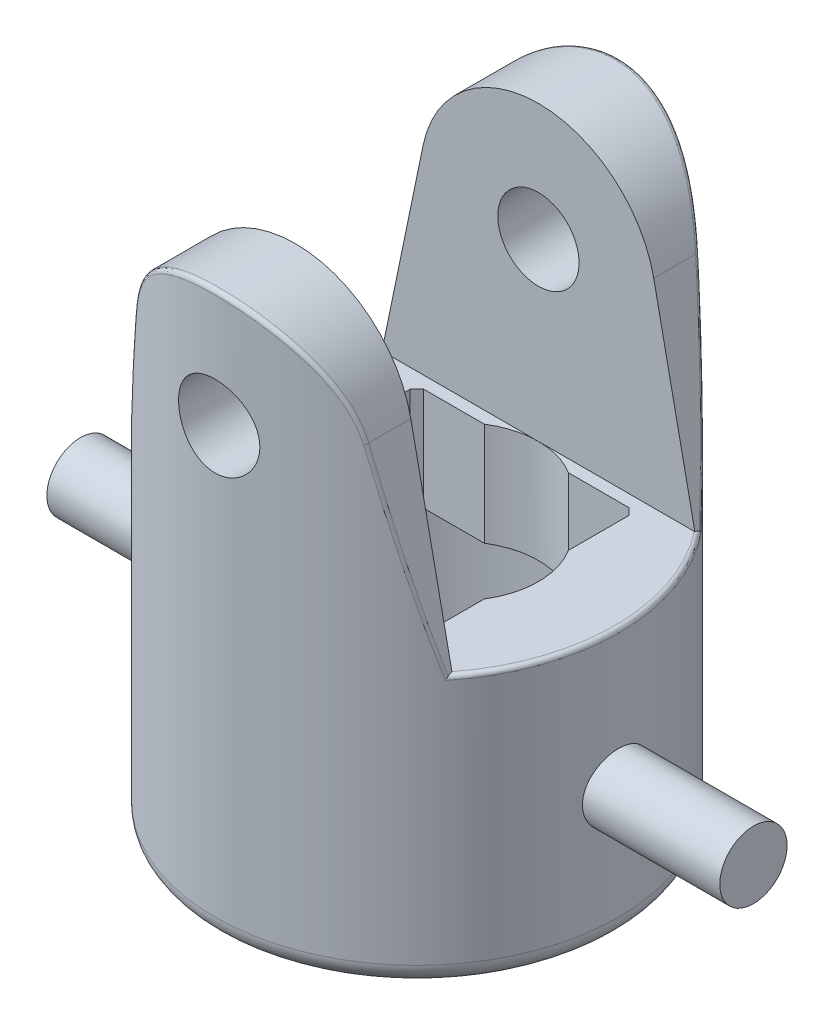
SolidWorks part; units mm, degrees
material "1023 Carbon Steel Sheet (SS)"
ref_plane "Front Plane" through (0, 0, 0) normal (0, 0, 1) x (1, 0, 0)
ref_plane "Top Plane" through (0, 0, 0) normal (0, 1, 0) x (1, 0, 0)
ref_plane "Right Plane" through (0, 0, 0) normal (1, 0, 0) x (0, 0, -1)
sketch "Sketch1" plane through (0, 0, 0) normal (0, 1, 0) x (1, 0, 0)
  circle A0 centre (0, 0) radius 12
  dimension "D1" = 24
extrude "Boss-Extrude1" add sketch "Sketch1" along normal blind 33.53
sketch "Sketch2" plane through (0, 0, 0) normal (0, -1, 0) x (1, 0, 0)
  line L0 (-2.5, 6.5) -> (-6.1, 6.5)
  line L1 (6.5, -6.5) -> (-6.5, -6.5) construction
  line L2 (6.5, -6.5) -> (6.5, 6.5) construction
  line L3 (-6.5, 6.1) -> (-6.5, 2.5)
  line L4 (-6.5, -6.5) -> (-6.5, 6.5) construction
  line L5 (6.5, -6.5) -> (-6.5, 6.5) construction
  line L6 (6.5, 6.5) -> (-6.5, -6.5) construction
  line L7 (-6.5, -2.5) -> (-6.5, -6.1)
  line L8 (-6.1, -6.5) -> (-2.5, -6.5)
  line L9 (2.5, -6.5) -> (6.1, -6.5)
  line L10 (6.5, -6.1) -> (6.5, -2.5)
  line L11 (6.5, 2.5) -> (6.5, 6.1)
  line L12 (6.1, 6.5) -> (2.5, 6.5)
  line L13 (-6.1, 6.5) -> (-6.5, 6.1)
  line L14 (-6.5, -6.1) -> (-6.1, -6.5)
  line L15 (6.1, -6.5) -> (6.5, -6.1)
  line L16 (6.5, 6.1) -> (6.1, 6.5)
  arc A0 (-2.5, 6.5) -> (2.5, 6.5) centre (0, 2.5201) cw
  arc A1 (6.5, 2.5) -> (6.5, -2.5) centre (2.5201, 0) cw
  arc A2 (2.5, -6.5) -> (-2.5, -6.5) centre (0, -2.5201) cw
  arc A3 (-6.5, -2.5) -> (-6.5, 2.5) centre (-2.5201, 0) cw
  point P0 (0, 0)
  point P21 (0, 0)
  dimension "D3" = 4.7
  dimension "D4" = 4
  dimension "D1" = 13
  dimension "D2" = 4
extrude "Cut-Extrude1" cut sketch "Sketch2" against normal blind 19.6
sketch "Sketch3" plane through (0, 0, 0) normal (0, -1, 0) x (1, 0, 0)
  circle A0 centre (0, 0) radius 9.375
  dimension "D1" = 18.75
fillet "Fillet1" radius 1.25 1 edges at (0, 0, 12)
sketch "Sketch4" plane through (0, 0, 0) normal (0, 0, 1) x (1, 0, 0)
  line L0 (-7.2, 5.7) -> (-7.2, 4.7)
  line L1 (-7.2, 4.7) -> (-6.6396, 4.9757)
  line L2 (-6.6396, 5.4243) -> (-7.2, 5.7)
  line L3 (-6.5, 19.6) -> (-6.5, 0) construction
  arc A0 (-6.6396, 4.9757) -> (-6.6396, 5.4243) centre (-6.75, 5.2) ccw
  point P5 (-6.1837, 5.2)
  dimension "D3" = 0.25
  dimension "D1" = 1
  dimension "D2" = 7.2
  dimension "D4" = 4.7
extrude "Boss-Extrude2" add sketch "Sketch4" against normal up to surface and the other way up to surface up to face at (-6.86, 9.8, 0) other way up to face at (-6.86, 9.8, 0)
ref_axis "Axis1" through (0, 35.4242, 0) along (0, -1, 0)
pattern_circular "CirPattern2" count 4 over 360 about axis through (0, 35.4242, 0) along (0, -1, 0) of "Boss-Extrude2"
sketch "Sketch5" plane through (0, 33.53, 0) normal (0, 1, 0) x (1, 0, 0)
  line L1 (12, -7.2201) -> (-12, -7.2201)
  line L2 (12, -7.2201) -> (12, 7.2201)
  line L3 (12, 7.2201) -> (-12, 7.2201)
  line L4 (-12, -7.2201) -> (-12, 7.2201)
  line L5 (12, -7.2201) -> (-12, 7.2201) construction
  line L6 (12, 7.2201) -> (-12, -7.2201) construction
  arc A0 (2.5, 6.5) -> (-2.5, 6.5) centre (0, 2.5201) ccw construction
  circle A1 centre (0, 0) radius 12 construction
  point P0 (0, 0)
extrude "Cut-Extrude3" cut sketch "Sketch5" against normal blind 17.4
sketch "Sketch6" plane through (0, 0, 0) normal (0, 0, 1) x (1, 0, 0)
  line L0 (12, 16.13) -> (9.3, 16.13)
  line L1 (9.3, 16.13) -> (6.8548, 27.9483)
  line L2 (-6.8548, 27.9483) -> (-9.3, 16.13)
  line L3 (-9.3, 16.13) -> (-12, 16.13)
  line L4 (9.5849, 33.53) -> (-9.5849, 33.53) construction
  arc A0 (6.8548, 27.9483) -> (-6.8548, 27.9483) centre (0, 26.53) ccw
  dimension "D2" = 7
  dimension "D1" = 2.7
extrude "Cut-Extrude6" cut sketch "Sketch6" against normal through all both and the other way through all flip side to cut
sketch "Sketch7" plane through (0, 0, 0) normal (0, 0, 1) x (1, 0, 0)
  circle A0 centre (0, 26.53) radius 2.415
  dimension "D1" = 4.83
extrude "Cut-Extrude7" cut sketch "Sketch7" against normal mid plane 52.4
fillet "Fillet2" radius 0.25 8 edges at (-8.1565, 21.657, -8.8018) (8.1565, 21.657, -8.8018) (8.1565, 21.657, 8.8018) (-8.1565, 21.657, 8.8018) (-12, 16.13, 0) (0, 33.53, -12) (12, 16.13, 0) (0.1168, 33.529, 11.9994)
sketch "Sketch8" plane through (0, 0, 0) normal (0, -1, 0) x (1, 0, 0)
  circle A0 centre (0, 0) radius 8.9806
extrude "Cut-Extrude8" cut sketch "Sketch8" against normal blind 10
sketch "Sketch9" plane through (0, 0, 0) normal (1, 0, 0) x (0, 0, -1)
  line L0 (0, 0) -> (0, 15.88) construction
  line L1 (7.5958, 15.88) -> (-7.5958, 15.88) construction
  circle A0 centre (0, 7.94) radius 2
extrude "Boss-Extrude3" add sketch "Sketch9" along normal blind 20 and the other way blind 20
